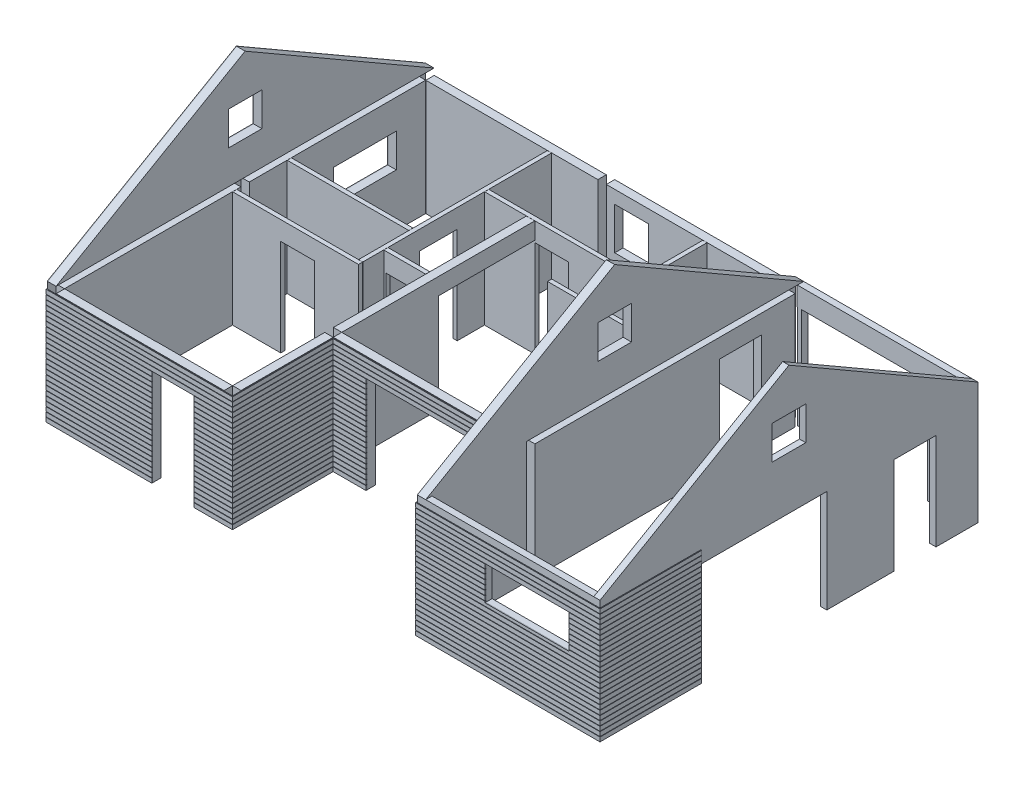
SolidWorks part; units mm, degrees
note: The reader was unsure of these and kept them because the rebuilt part matched: shared geometry of "Эскиз8<2>".
ref_plane "Спереди" through (0, 0, 0) normal (0, 0, 1) x (1, 0, 0)
ref_plane "Сверху" through (0, 0, 0) normal (0, 1, 0) x (1, 0, 0)
ref_plane "Справа" through (0, 0, 0) normal (1, 0, 0) x (0, 0, -1)
sketch "Эскиз1" plane through (0, 0, 0) normal (0, 1, 0) x (1, 0, 0)
  line L0 (9000, -6600) -> (4400, -6600) construction
  line L1 (0, 0) -> (9000, 0) construction
  line L2 (0, 0) -> (0, -8800) construction
  line L3 (0, -9000) -> (4400, -9000) construction
  line L4 (9000, 0) -> (9000, -6600) construction
  line L5 (4400, -6600) -> (4400, -9000) construction
  line L6 (8800, -203) -> (9000, -203)
  line L7 (203, 0) -> (4300, 0)
  line L8 (203, 0) -> (203, -200)
  line L9 (203, -200) -> (4300, -200)
  line L12 (0, -200) -> (0, -4400)
  line L14 (200, -200) -> (200, -4400)
  line L15 (203, -9000) -> (2500, -9000)
  line L16 (203, -9000) -> (203, -8800)
  line L17 (203, -8800) -> (2500, -8800)
  line L19 (4400, -8797) -> (4200, -8797)
  line L20 (4400, -8797) -> (4400, -6603)
  line L22 (4200, -8797) -> (4200, -6603)
  line L24 (9000, -203) -> (9000, -1000)
  line L26 (8800, -203) -> (8800, -1000)
  line L27 (8797, -6600) -> (7597, -6600)
  line L28 (8797, -6600) -> (8797, -6400)
  line L29 (8797, -6400) -> (7597, -6400)
  line L31 (2500, -8800) -> (2500, -9000)
  line L32 (3500, -8800) -> (3500, -9000)
  line L33 (3500, -8800) -> (4200, -8800)
  line L34 (3500, -9000) -> (4200, -9000)
  line L35 (5597, -6400) -> (5597, -6600)
  line L36 (7597, -6400) -> (7597, -6600)
  line L37 (5597, -6400) -> (4400, -6400)
  line L38 (5597, -6600) -> (4400, -6600)
  line L39 (8800, -1000) -> (9000, -1000)
  line L41 (8800, -2000) -> (9000, -2000)
  line L42 (8800, -2000) -> (8800, -6400)
  line L43 (9000, -2000) -> (9000, -6400)
  line L47 (4200, -6397) -> (4400, -6397)
  line L83 (4200, -6603) -> (4400, -6603)
  line L92 (4200, -4100) -> (4400, -4100)
  line L93 (4200, -4100) -> (4200, -6397)
  line L94 (4400, -4100) -> (4400, -6397)
  line L100 (200, -8800) -> (0, -8800)
  line L101 (4200, -8800) -> (4200, -9000)
  line L102 (4400, -6400) -> (4400, -6600)
  line L103 (8800, -6400) -> (9000, -6400)
  line L104 (0, -200) -> (200, -200)
  line L105 (0, -4400) -> (200, -4400)
  line L107 (0, -4600) -> (200, -4600)
  line L108 (0, -4600) -> (0, -8800)
  line L109 (200, -4600) -> (200, -8800)
  line L110 (8800, 0) -> (8800, -200)
  line L111 (4300, 0) -> (4300, -200)
  line L113 (4500, 0) -> (4500, -200)
  line L114 (4500, 0) -> (8800, 0)
  line L115 (4500, -200) -> (8800, -200)
  line L116 (0, -9000) -> (0, -8800) construction
  line L117 (-6170.9643, 0) -> (12200, 0) construction
  line L118 (0, 1882.3698) -> (0, -11726.3327) construction
  line L119 (-6170.9643, -4500) -> (10764.3505, -4500) construction
  line L120 (2148.439, -4700) -> (3200, -4700)
  line L121 (-6170.9643, -9000) -> (12200, -9000) construction
  line L122 (2148.439, -4700) -> (2148.439, -4800)
  line L123 (2148.439, -4800) -> (3200, -4800)
  line L124 (3200, -4700) -> (3200, -4800)
  line L125 (2148.439, -4700) -> (3200, -4800) construction
  line L126 (2148.439, -4800) -> (3200, -4700) construction
  line L127 (203, -4700) -> (1348.439, -4700)
  line L128 (203, -4700) -> (203, -4800)
  line L129 (203, -4800) -> (1348.439, -4800)
  line L130 (1348.439, -4700) -> (1348.439, -4800)
  line L131 (203, -4700) -> (1348.439, -4800) construction
  line L132 (203, -4800) -> (1348.439, -4700) construction
  line L137 (3100, -203) -> (3200, -203)
  line L138 (3100, -203) -> (3100, -2450)
  line L139 (3100, -2450) -> (3200, -2450)
  line L140 (3200, -203) -> (3200, -2450)
  line L141 (3100, -203) -> (3200, -2450) construction
  line L142 (3100, -2450) -> (3200, -203) construction
  line L143 (3100, -3350) -> (3200, -3350)
  line L144 (3100, -3350) -> (3100, -4697)
  line L145 (3100, -4697) -> (3200, -4697)
  line L146 (3200, -3350) -> (3200, -4697)
  line L147 (3100, -3350) -> (3200, -4697) construction
  line L148 (3100, -4697) -> (3200, -3350) construction
  line L149 (4150, -4100) -> (4197, -4100)
  line L150 (4150, -4100) -> (4150, -4200)
  line L151 (4150, -4200) -> (4197, -4200)
  line L152 (4197, -4100) -> (4197, -4200)
  line L153 (4150, -4100) -> (4197, -4200) construction
  line L154 (4150, -4200) -> (4197, -4100) construction
  line L155 (203, -3400) -> (3097, -3400)
  line L156 (203, -3400) -> (203, -3500)
  line L157 (203, -3500) -> (3097, -3500)
  line L158 (3097, -3400) -> (3097, -3500)
  line L159 (203, -3400) -> (3097, -3500) construction
  line L160 (203, -3500) -> (3097, -3400) construction
  line L161 (6400, -3503) -> (8800, -3503) construction
  line L162 (4400, 2182.3698) -> (4400, -11426.3327) construction
  line L163 (5200, -1700) -> (6900, -1700)
  line L164 (9000, 2182.3698) -> (9000, -11265.4622) construction
  line L165 (5200, -1700) -> (5200, -1800)
  line L166 (5200, -1800) -> (6900, -1800)
  line L167 (6900, -1700) -> (6900, -1800)
  line L168 (5200, -1700) -> (6900, -1800) construction
  line L169 (5200, -1800) -> (6900, -1700) construction
  line L170 (5800, -2800) -> (8797, -2800)
  line L171 (5800, -2800) -> (5800, -2900)
  line L172 (5800, -2900) -> (8797, -2900)
  line L173 (8797, -2800) -> (8797, -2900)
  line L174 (5800, -2800) -> (8797, -2900) construction
  line L175 (5800, -2900) -> (8797, -2800) construction
  line L176 (6800, -203) -> (6900, -203)
  line L177 (6800, -203) -> (6800, -1697)
  line L178 (6800, -1697) -> (6900, -1697)
  line L179 (6900, -203) -> (6900, -1697)
  line L180 (6800, -203) -> (6900, -1697) construction
  line L181 (6800, -1697) -> (6900, -203) construction
  line L186 (3203, -1700) -> (4400, -1700)
  line L187 (3203, -1700) -> (3203, -1800)
  line L188 (3203, -1800) -> (4400, -1800)
  line L189 (4400, -1700) -> (4400, -1800)
  line L190 (3203, -1700) -> (4400, -1800) construction
  line L191 (3203, -1800) -> (4400, -1700) construction
  line L192 (5800, -2903) -> (6400, -2903) construction
  line L193 (5800, -2903) -> (5800, -3503) construction
  line L194 (5800, -3503) -> (6400, -3503) construction
  line L195 (6400, -2903) -> (6400, -3503) construction
  line L196 (5800, -2903) -> (6400, -3503) construction
  line L197 (5800, -3503) -> (6400, -2903) construction
  line L198 (12200, 0) -> (12200, -9000) construction
  line L199 (5403, -4397) -> (5800, -3503) construction
  line L204 (3203, -4100) -> (3250, -4100)
  line L205 (3203, -4100) -> (3203, -4200)
  line L206 (3203, -4200) -> (3250, -4200)
  line L207 (3250, -4100) -> (3250, -4200)
  line L208 (3203, -4100) -> (3250, -4200) construction
  line L209 (3203, -4200) -> (3250, -4100) construction
  line L210 (4403, -4397) -> (5403, -4397) construction
  line L211 (4403, -4397) -> (4403, -6397) construction
  line L212 (4403, -6397) -> (5403, -6397) construction
  line L213 (5403, -4397) -> (5403, -6397) construction
  line L214 (4403, -4397) -> (5403, -6397) construction
  line L215 (4403, -6397) -> (5403, -4397) construction
  point P14 (3226.5, -4150)
  point P17 (7298.5, -2850)
  point P38 (775.7195, -4750)
  point P41 (2674.2195, -4750)
  point P52 (3150, -1326.5)
  point P53 (775.7195, -4750)
  point P62 (3150, -4023.5)
  point P67 (4173.5, -4150)
  point P72 (1650, -3450)
  point P103 (3801.5, -1750)
  point P104 (6850, -950)
  point P105 (4150, -4150)
  point P108 (6050, -1750)
  point P120 (6800, -950)
  point P122 (6100, -3203)
  point P127 (4903, -5397)
  dimension "D2" = 6600
  dimension "D3" = 9000
  dimension "D4" = 200
  dimension "D5" = 3
  dimension "D6" = 3
  dimension "D7" = 3
  dimension "D8" = 9000
  dimension "D9" = 200
  dimension "D10" = 3
  dimension "D11" = 3
  dimension "D12" = 700
  dimension "D13" = 50
  dimension "D14" = 4500
  dimension "D15" = 4000
  dimension "D16" = 4200
  dimension "D17" = 4200
  dimension "D18" = 4400
  dimension "D19" = 4600
  dimension "D20" = 1000
  dimension "D21" = 4000
  dimension "D22" = 2000
  dimension "D23" = 1200
  dimension "D24" = 1000
  dimension "D25" = 3
  dimension "D26" = 200
  dimension "D27" = 3
  dimension "D28" = 3
  dimension "D29" = 800
  dimension "D30" = 4500
  dimension "D31" = 3
  dimension "D32" = 3
  dimension "D33" = 3
  dimension "D34" = 900
  dimension "D35" = 3
  dimension "D36" = 900
  dimension "D37" = 50
  dimension "D38" = 3
  dimension "D39" = 3
  dimension "D40" = 100
  dimension "D41" = 2900
  dimension "D42" = 3200
  dimension "D43" = 1200
  dimension "D44" = 200
  dimension "D45" = 3
  dimension "D46" = 3600
  dimension "D47" = 1500
  dimension "D48" = 800
  dimension "D49" = 1900
  dimension "D50" = 1000
  dimension "D51" = 3
  dimension "D52" = 3
  dimension "D53" = 800
  dimension "D54" = 3
  dimension "D55" = 4400
  dimension "D56" = 3500
  dimension "D57" = 2400
  dimension "D58" = 3000
  dimension "D59" = 1400
  dimension "D60" = 2700
  dimension "D61" = 600
  dimension "D62" = 3
  dimension "D63" = 2897
  dimension "D64" = 2300
  dimension "D65" = 1197
  dimension "D66" = 3200
  dimension "D67" = 2000
  dimension "D68" = 1000
  dimension "D69" = 3
  dimension "D70" = 3
  dimension "D72" = 200
  dimension "D73" = 200
extrude "Бобышка-Вытянуть3" add sketch "Эскиз1" along normal blind 2750
sketch "Эскиз2" plane through (0, 0, 0) normal (-1, 0, 0) x (0, 0, 1)
  line L2 (900, 1250) -> (2400, 1250)
  line L3 (900, 1250) -> (900, 2050)
  line L4 (900, 2050) -> (2400, 2050)
  line L5 (2400, 1250) -> (2400, 2050)
  line L7 (200, 0) -> (4400, 0) construction
  line L8 (3400, 2750) -> (3400, 0) construction
  dimension "D1" = 1500
  dimension "D2" = 800
  dimension "D3" = 1250
  dimension "D4" = 1000
extrude "Вырез-Вытянуть2" cut sketch "Эскиз2" against normal blind 250
sketch "Эскиз3" plane through (0, 0, 0) normal (0, 0, -1) x (-1, 0, 0)
  line L0 (-4500, 0) -> (-8800, 0) construction
  line L8 (-5500, 2440) -> (-4700, 2440)
  line L9 (-5500, 2440) -> (-5500, 1440)
  line L10 (-5500, 1440) -> (-4700, 1440)
  line L11 (-4700, 2440) -> (-4700, 1440)
  line L15 (-4500, 2750) -> (-4500, 0) construction
  dimension "D1" = 200
  dimension "D2" = 2440
  dimension "D3" = 800
  dimension "D4" = 1000
  dimension "D5" = 1440
extrude "Вырез-Вытянуть3" cut sketch "Эскиз3" against normal blind 593
sketch "Эскиз4" plane through (0, 2750, 0) normal (0, 1, 0) x (1, 0, 0)
  line L0 (203, -4700) -> (1348.439, -4700) construction
  line L1 (1298.6372, -4700) -> (2231.668, -4700)
  line L2 (1298.6372, -4700) -> (1298.6372, -4800)
  line L3 (1298.6372, -4800) -> (2231.668, -4800)
  line L4 (2231.668, -4700) -> (2231.668, -4800)
  line L5 (2148.439, -4800) -> (3200, -4800) construction
  line L6 (3203, -4100) -> (3250, -4100) construction
  line L7 (3226.5, -4100) -> (4173.5, -4100)
  line L8 (3226.5, -4100) -> (3226.5, -4200)
  line L9 (3226.5, -4200) -> (4173.5, -4200)
  line L10 (4173.5, -4100) -> (4173.5, -4200)
  line L11 (4150, -4200) -> (4197, -4200) construction
  line L12 (3100, -203) -> (3100, -2450) construction
  line L13 (3100, -2329.5149) -> (3200, -2329.5149)
  line L14 (3100, -2329.5149) -> (3100, -3395.1608)
  line L15 (3100, -3395.1608) -> (3200, -3395.1608)
  line L16 (3200, -2329.5149) -> (3200, -3395.1608)
  line L17 (3200, -3350) -> (3200, -4697) construction
  line L18 (3203, -1700) -> (4400, -1700) construction
  line L19 (4236.0845, -1700) -> (5342.3733, -1700)
  line L20 (4236.0845, -1700) -> (4236.0845, -1800)
  line L21 (4236.0845, -1800) -> (5342.3733, -1800)
  line L22 (5342.3733, -1700) -> (5342.3733, -1800)
  line L23 (5200, -1800) -> (6900, -1800) construction
  line L30 (5597, -6400) -> (4400, -6400) construction
  line L31 (5423.0031, -6400) -> (7690.4362, -6400)
  line L32 (5423.0031, -6400) -> (5423.0031, -6600)
  line L33 (5423.0031, -6600) -> (7690.4362, -6600)
  line L34 (7690.4362, -6400) -> (7690.4362, -6600)
  line L35 (8797, -6600) -> (7597, -6600) construction
  line L36 (8800, -203) -> (8800, -1000) construction
  line L37 (8800, -900.8258) -> (9000, -900.8258)
  line L38 (8800, -900.8258) -> (8800, -2153.976)
  line L39 (8800, -2153.976) -> (9000, -2153.976)
  line L40 (9000, -900.8258) -> (9000, -2153.976)
  line L41 (9000, -2000) -> (9000, -6400) construction
  line L42 (3500, -9000) -> (4200, -9000) construction
  line L43 (2379.0159, -8797) -> (3597.5552, -8797)
  line L44 (2379.0159, -8797) -> (2379.0159, -9000)
  line L45 (2379.0159, -9000) -> (3597.5552, -9000)
  line L46 (3597.5552, -8797) -> (3597.5552, -9000)
extrude "Бобышка-Вытянуть4" add sketch "Эскиз4" against normal offset from surface (450 mm away) 2300 up to face at (8900, 0, 601.5)
ref_plane "Плоскость1" through (13000, 0, 0) normal (1, 0, 0) x (0, 0, -1)
sketch "Эскиз5" plane through (13000, 0, 0) normal (1, 0, 0) x (0, 0, -1)
  line L0 (-4500, 5671.2813) -> (-4500, -200) construction
  line L1 (-6600, -200) -> (0, -200) construction
  line L2 (-4500, 5498.0762) -> (-9000, 2900)
  line L3 (-9000, 2900) -> (-9000, -200)
  line L4 (-9000, -200) -> (0, -200)
  line L5 (0, 2900) -> (0, -200)
  line L6 (-4500, 5498.0762) -> (0, 2900)
extrude "Бобышка-Вытянуть5" add sketch "Эскиз5" along normal blind 150 separate body
sketch "Эскиз6" plane through (13000, 0, 0) normal (1, 0, 0) x (0, 0, -1)
  line L0 (-9000, -200) -> (0, -200) construction
  line L1 (-1000, 2300) -> (-2000, 2300)
  line L2 (-1000, 2300) -> (-1000, -200)
  line L3 (-1000, -200) -> (-2000, -200)
  line L4 (-2000, 2300) -> (-2000, -200)
  line L5 (0, 2444.3376) -> (50, 2444.3376) construction
  line L6 (-6600, -200) -> (-3600, -200)
  line L7 (-6600, -200) -> (-6600, 2444.3376)
  line L8 (-6600, 2444.3376) -> (-3600, 2444.3376)
  line L9 (-3600, -200) -> (-3600, 2444.3376)
  dimension "D1" = 3000
extrude "Вырез-Вытянуть5" cut sketch "Эскиз6" along normal blind 670
sketch "Эскиз7" plane through (0, 0, 0) normal (0, 1, 0) x (1, 0, 0)
  line L1 (0, -4600) -> (0, -9000)
  line L2 (0, -4600) -> (0, -8800) construction
  line L3 (0, -9000) -> (4400, -9000)
  line L4 (4400, -9000) -> (4400, -6603)
  line L5 (4400, -6603) -> (8800, -6600.0667)
  line L7 (8800, -6600.0667) -> (8800, -9000)
  line L8 (8800, -9000) -> (13150, -9000)
  line L9 (13150, -9000) -> (13150, -6600)
  line L10 (8800, -203) -> (8800, -6400) construction
  line L11 (13150, -4500) -> (13150, -9000) construction
  line L12 (-20, -4600) -> (-20, -9020)
  line L13 (-20, -9020) -> (4420, -9020)
  line L14 (4420, -9020) -> (4420, -6622.9867)
  line L15 (4420, -6622.9867) -> (8780, -6620.08)
  line L16 (8780, -6620.08) -> (8780, -9020)
  line L17 (8780, -9020) -> (13170, -9020)
  line L18 (13170, -9020) -> (13170, -6600)
  line L19 (0, -4600) -> (-20, -4600)
  line L20 (13150, -6600) -> (13170, -6600)
  dimension "D1" = 20
extrude "Бобышка-Вытянуть7" add sketch "Эскиз7" along normal blind 100 separate body
sketch "Эскиз8" plane through (0, 0, 0) normal (-1, 0, 0) x (0, 0, 1)
  line L0 (4500, 5498.0762) -> (0, 2900)
  line L1 (0, 2900) -> (9000, 2900)
  line L2 (9000, 2900) -> (4500, 5498.0762)
  line L3 (4500, 5498.0762) -> (4500, 2900) construction
  line L4 (2400, 1250) -> (2400, 2050) construction
  line L5 (4100, 4500) -> (4900, 4500)
  line L6 (4100, 4500) -> (4100, 3700)
  line L7 (4100, 3700) -> (4900, 3700)
  line L8 (4900, 4500) -> (4900, 3700)
  dimension "D1" = 800
extrude "Бобышка-Вытянуть8" add sketch "Эскиз8" against normal up to surface (200 mm away) separate body up to face at (200, 1375, 6700)
sketch "Эскиз9" plane through (9000, 0, 0) normal (1, 0, 0) x (0, 0, -1)
  line L0 (-6600, -200) -> (-6600, 2900)
  line L1 (-6600, 2750) -> (-6600, 0) construction
  line L2 (-6600, 2900) -> (0, 2900)
  line L3 (0, 2900) -> (-4500, 5498.0762)
  line L4 (-4500, 5498.0762) -> (-9000, 2900)
  line L5 (-9000, 2900) -> (-9000, -200)
  line L6 (-9000, -200) -> (-6600, -200)
extrude "Бобышка-Вытянуть9" add sketch "Эскиз9" against normal blind 200 separate body
sketch "Эскиз10" plane through (0, -200, 0) normal (0, -1, 0) x (1, 0, 0)
  line L0 (13000, 9000) -> (13000, 6600) construction
  line L1 (9000, 9000) -> (13000, 9000)
  line L2 (9000, 9000) -> (9000, 8850)
  line L3 (9000, 8850) -> (13000, 8850)
  line L4 (13000, 9000) -> (13000, 8850)
  line L5 (13150, 9000) -> (13000, 9000) construction
  line L6 (9000, 6600) -> (9000, 0) construction
  line L7 (13000, 0) -> (12100, 0)
  line L8 (13000, 0) -> (13000, 150)
  line L9 (13000, 150) -> (12100, 150)
  line L10 (12100, 0) -> (12100, 150)
  line L11 (9000, 150) -> (9100, 150)
  line L12 (9000, 150) -> (9000, 0)
  line L13 (9000, 0) -> (9100, 0)
  line L14 (9100, 150) -> (9100, 0)
extrude "Бобышка-Вытянуть10" add sketch "Эскиз10" against normal up to vertex (3100 mm away) up to point (9000, 2900, 9000)
pattern_linear "Линейный массив1" count 25 spacing 110 along (0, 1, 0) of "Бобышка-Вытянуть7"
sketch "Эскиз11" plane through (0, 0, 6400) normal (0, 0, -1) x (-1, 0, 0)
  line L1 (-7597, 2300) -> (-5200, 2300)
  line L2 (-7597, 2300) -> (-7597, -335.5255)
  line L3 (-7597, -335.5255) -> (-5200, -335.5255)
  line L4 (-5200, 2300) -> (-5200, -335.5255)
  line L5 (20, 2300) -> (-4420, 2300) construction
  line L6 (-2500, 2300) -> (-3500, 2300)
  line L7 (-2500, 2300) -> (-2500, -123.1481)
  line L8 (-2500, -123.1481) -> (-3500, -123.1481)
  line L9 (-3500, 2300) -> (-3500, -123.1481)
  line L10 (-8780, 2300) -> (-13170, 2300) construction
  line L11 (-10431.0972, 2300) -> (-12431.0972, 2300)
  line L12 (-10431.0972, 2300) -> (-10431.0972, 1500)
  line L13 (-10431.0972, 1500) -> (-12431.0972, 1500)
  line L14 (-12431.0972, 2300) -> (-12431.0972, 1500)
  dimension "D1" = 2000
  dimension "D2" = 800
  dimension "D3" = 2397
extrude "Вырез-Вытянуть6" cut sketch "Эскиз11" against normal blind 5123
sketch "Эскиз12" plane through (0, 0, 0) normal (-1, 0, 0) x (0, 0, 1)
  line L0 (2424.8711, 2900) -> (2424.8711, 4300) construction
  line L1 (0, 2900) -> (9000, 2900) construction
  line L2 (4500, 5498.0762) -> (0, 2900) construction
  line L3 (2424.8711, 4300) -> (3290.8965, 4800) construction
  line L4 (3290.8965, 4800) -> (5709.1035, 4800) construction
  line L5 (9000, 2900) -> (4500, 5498.0762) construction
  line L6 (5709.1035, 4800) -> (6575.1289, 4300) construction
  line L7 (6575.1289, 4300) -> (6575.1289, 2900) construction
  line L8 (4500, 5498.0762) -> (4500, 4800) construction
  dimension "D1" = 1900
  dimension "D2" = 2418.2069
  dimension "D3" = 1400
  dimension "D4" = 4150.2577
extrude "Вырез-Вытянуть7" cut sketch "Эскиз8<2>" against normal blind 16606 contours L5 L8 L7 L6
sketch "Эскиз8<2>" plane through (0, 0, 0) normal (-1, 0, 0) x (0, 0, 1) same geometry as "Эскиз8"
sketch "Эскиз13" plane through (0, 0, 0) normal (-1, 0, 0) x (0, 0, 1)
  line L0 (4500, 5498.0762) -> (0, 2900)
  line L1 (0, 2900) -> (0, 0)
  line L2 (0, 0) -> (9000, 0)
  line L3 (9000, 2900) -> (9000, -200) construction
  line L4 (4500, 5498.0762) -> (9000, 2900)
  line L5 (9000, 2900) -> (9000, 0)
  line L7 (4100, 4500) -> (4900, 4500)
  line L8 (4100, 4500) -> (4100, 3700)
  line L9 (4100, 3700) -> (4900, 3700)
  line L10 (4900, 4500) -> (4900, 3700)
  line L11 (900, 2050) -> (2400, 2050)
  line L12 (900, 2050) -> (900, 1250)
  line L13 (900, 1250) -> (2400, 1250)
  line L14 (2400, 2050) -> (2400, 1250)
extrude "Штукатурка-фасад" add sketch "Эскиз13" along normal blind 10 separate body
sketch "Эскиз14" plane through (0, 0, 0) normal (0, 0, -1) x (-1, 0, 0)
  line L1 (-8670.1796, 0) -> (-13504.1539, 0)
  line L2 (-8670.1796, 0) -> (-8670.1796, -577.2384)
  line L3 (-8670.1796, -577.2384) -> (-13504.1539, -577.2384)
  line L4 (-13504.1539, 0) -> (-13504.1539, -577.2384)
extrude "Вырез-Вытянуть8" cut sketch "Эскиз14" against normal blind 9961
sketch "Эскиз16" plane through (13150, 0, 0) normal (1, 0, 0) x (0, 0, -1)
  line L0 (-150, 2900) -> (-150, 0) construction
  line L1 (0, 2900) -> (-150, 2900)
  line L2 (0, 2900) -> (0, 2444.3376)
  line L3 (0, 2444.3376) -> (-150, 2444.3376)
  line L4 (-150, 2900) -> (-150, 2444.3376)
  line L5 (-3600, 2444.3376) -> (-6600, 2444.3376) construction
extrude "Бобышка-Вытянуть16" add sketch "Эскиз16" against normal blind 4160
sketch "Эскиз17" plane through (0, 0, 4100) normal (0, 0, -1) x (-1, 0, 0)
  line L0 (-4200, 2750) -> (-4200, 0) construction
  line L1 (-4400, 2750) -> (-4200, 2750)
  line L2 (-4400, 2750) -> (-4400, 2350)
  line L3 (-4400, 2350) -> (-4200, 2350)
  line L4 (-4200, 2750) -> (-4200, 2350)
  dimension "D1" = 400
extrude "Бобышка-Вытянуть17" add sketch "Эскиз17" along normal blind 2297
